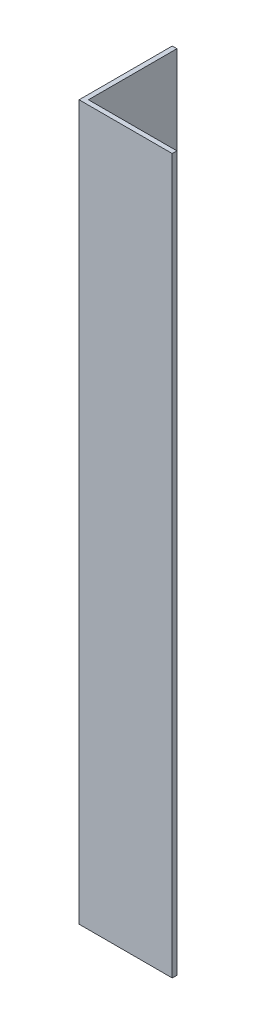
SolidWorks part; units mm, degrees
material "1060 Сплав"
ref_plane "Спереди" through (0, 0, 0) normal (0, 0, 1) x (1, 0, 0)
ref_plane "Сверху" through (0, 0, 0) normal (0, 1, 0) x (1, 0, 0)
ref_plane "Справа" through (0, 0, 0) normal (1, 0, 0) x (0, 0, -1)
sketch "Эскиз1" plane through (0, 0, 0) normal (0, 1, 0) x (1, 0, 0)
  line L0 (0, 0) -> (0, 15)
  line L1 (0, 15) -> (0.75, 15)
  line L2 (0.75, 15) -> (0.75, 0.75)
  line L3 (0.75, 0.75) -> (15, 0.75)
  line L4 (15, 0.75) -> (15, 0)
  line L5 (15, 0) -> (0, 0)
  dimension "D1" = 0.75
  dimension "D2" = 15
extrude "Бобышка-Вытянуть1" add sketch "Эскиз1" along normal blind 115
